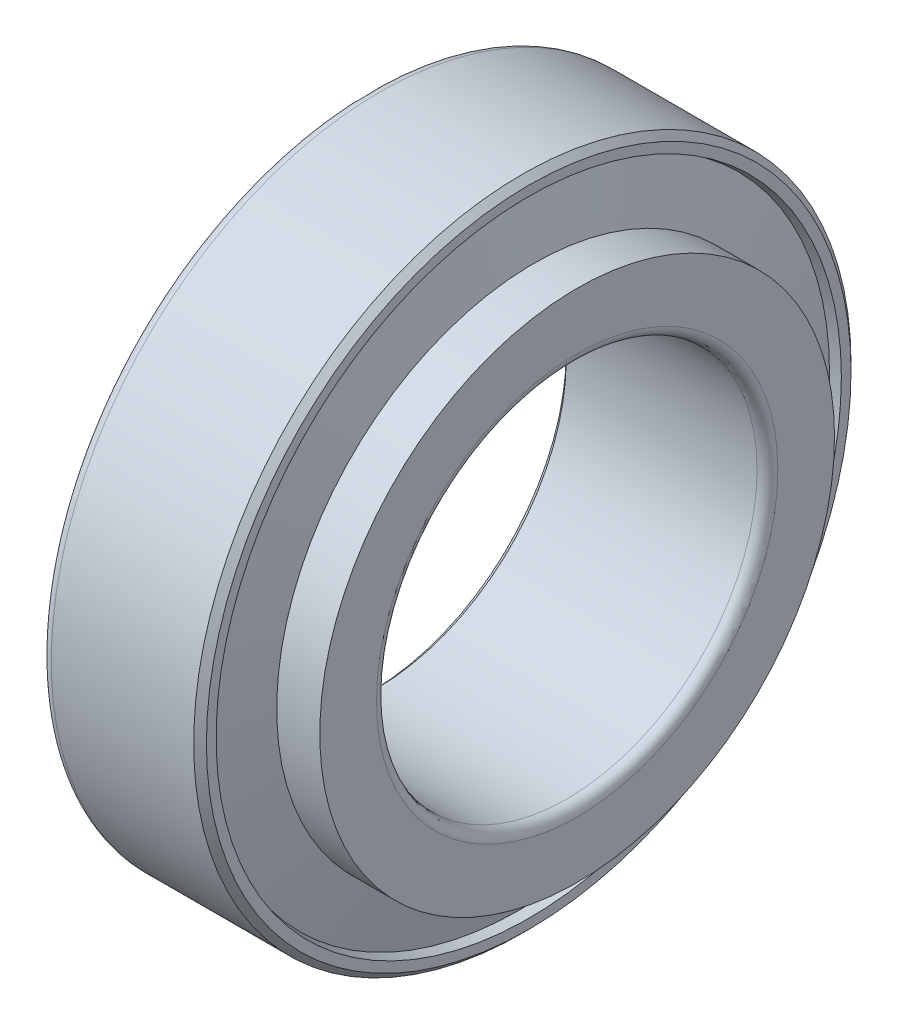
SolidWorks part; units mm, degrees
revolve "OuterRace" add sketch "OutRacSke" angle 360 about L5 other way angle 28.04 reverse direction yes
sketch "OutRacSke" plane through (0, 0, 0) normal (0, 0, 1) x (1, 0, 0)
  line L0 (-7, 45.1815) -> (-30, 39.447)
  line L1 (-30, 39.447) -> (-30, 46)
  line L2 (-28.5, 47.5) -> (-7.92, 47.5)
  line L3 (-7.92, 47.5) -> (-7, 46.58)
  line L4 (-7, 46.58) -> (-7, 45.1815)
  line L5 (-42.5, 0) -> (42.5, 0) construction
  arc A0 (-30, 46) -> (-28.5, 47.5) centre (-28.5, 46) cw
  dimension "D8" = 45
  dimension "Tangle" = 14
ref_plane "Plane1" through (0, 0, 0) normal (0, 0, 1) x (1, 0, 0)
ref_plane "Plane2" through (0, 0, 0) normal (0, 1, 0) x (1, 0, 0)
ref_plane "Plane3" through (0, 0, 0) normal (1, 0, 0) x (0, 0, -1)
sketch "Clipboard" plane through (0, 0, 0) normal (0, 0, 1) x (1, 0, 0)
  line L0 (0, 0) -> (10, 0) construction
  line L1 (0, 0) -> (78.8459, -2.7534)
  line L2 (0, 0) -> (54.9665, 1.9195)
  line L3 (0, 0) -> (94.9421, -3.3155)
  line L4 (0, 0) -> (-20.6968, -0.3613)
  line L5 (0, 0) -> (-9, 30)
  dimension "Roller_diameter" = 9
  dimension "cyl_len" = 20.7
sketch "RolDetSke" plane through (0, 0, 0) normal (0, 0, 1) x (1, 0, 0)
  line L0 (-27.4114, 35.6538) -> (-28.5, 40.0201)
  line L1 (-27.4114, 35.6538) -> (-7.3262, 40.6615)
  line L2 (-8.4149, 45.0279) -> (-7.3262, 40.6615)
  line L4 (-44.0239, 31.5118) -> (5.8616, 43.9497) construction
  line L5 (-8.4149, 45.0279) -> (-28.5, 40.0201)
  line L9 (-7, 45.1815) -> (-30, 39.447) construction
  dimension "Roller_diameter" = 9
  dimension "dy" = 40.0201
  dimension "D2" = 28.5
  dimension "cyl_len" = 20.7
revolve "RollerDetailed" [suppressed] add sketch "RolDetSke" angle 360 about L4 reverse direction yes
sketch "RolSimSke" plane through (0, 0, 0) normal (0, 0, 1) x (1, 0, 0)
  line L0 (0, 0) -> (-32, 0) construction
  line L1 (-28.5, 40.0201) -> (-8.4149, 45.0279)
  line L2 (-28.5, 40.0201) -> (-26.3227, 31.2874)
  line L3 (-26.3227, 31.2874) -> (-6.2376, 36.2952)
  line L4 (-8.4149, 45.0279) -> (-6.2376, 36.2952)
  dimension "Roller_diameter" = 9
  dimension "dy" = 40.0201
  dimension "dx" = 28.5
  dimension "Tangle" = 14
revolve "RollersSimplified" add sketch "RolSimSke" angle 360 about L0
ref_axis "Axis1" through (-50, 0, 0) along (1, 0, 0)
pattern_circular "RollersDetailed" [suppressed] count 2 every 180 about axis through (-50, 0, 0) along (1, 0, 0)
sketch "InsRacSke" plane through (0, 0, 0) normal (0, 0, 1) x (1, 0, 0)
  line L0 (-26.424, 31.7374) -> (-30, 31.7374)
  line L1 (-30, 46) -> (-30, -46) construction
  line L2 (-30, 31.7374) -> (-30, 28.42)
  line L3 (-30, 28.42) -> (-29.08, 27.5)
  line L4 (-29.08, 27.5) -> (-1.5, 27.5)
  line L5 (0, 29) -> (0, 37.1952)
  line L6 (0, 37.1952) -> (-6.2267, 37.1952)
  line L7 (-6.2267, 37.1952) -> (-6.2267, 36.2952)
  line L8 (-6.2267, 36.2952) -> (-26.3118, 31.2874)
  line L9 (-26.3118, 31.2874) -> (-26.424, 31.7374)
  line L10 (-42.5, 0) -> (42.5, 0) construction
  arc A0 (-1.5, 27.5) -> (0, 29) centre (-1.5, 29) ccw
  dimension "Tangle" = 14
  dimension "cyl_len" = 20.7
  dimension "dy" = 31.2874
  dimension "dx" = 26.3118
  dimension "D11" = 45
  dimension "D2" = 30
revolve "InnerRace" add sketch "InsRacSke" angle 360 about L10 reverse direction yes
sketch "CagSpiSke" plane through (0, 0, 0) normal (0, 0, 1) x (1, 0, 0)
  line L3 (-6.322, 40.7128) -> (-27.4114, 35.4547)
  line L4 (-27.8484, 34.7273) -> (-27.5581, 33.563)
  line L6 (-42.5, 0) -> (42.5, 0) construction
  arc A1 (-27.4114, 35.4547) -> (-27.8484, 34.7273) centre (-27.2662, 34.8725) ccw
  dimension "Tangle" = 14
  dimension "radius" = 0.6
  dimension "dx" = 27.4114
  dimension "dy" = 35.4547
  dimension "offset" = 1.8
revolve "CageSpine" [suppressed] add sketch "CagSpiSke" angle 0.001 about L6 wall 1.5
equation "\"OD@OutRacSke\" = \"Race_OD@Clipboard\""
equation "\"cup_SID@OutRacSke\" = \"Race_ID@Clipboard\""
equation "\"chamfer@OutRacSke\" = \"cup_width@OutRacSke\" / 25"
equation "\"offset@OutRacSke\" = \"OA_width@Clipboard\""
equation "\"D2@RolDetSke\" = \"offset@OutRacSke\" - \"cup_radius@OutRacSke\""
equation "\"dy@RolDetSke\" =  ( ( \"Race_ID@Clipboard\" / 2 ) + ( \"cup_radius@OutRacSke\" ) * tan(\"Tangle@OutRacSke\" * 3.141592654/180) ) * 1.005"
equation "\"cyl_len@RolDetSke\" = \"cyl_len@Clipboard\""
equation "\"Roller_diameter@RolDetSke\" = \"Roller_diameter@Clipboard\""
equation "\"dx@RolSimSke\" = \"offset@OutRacSke\" - \"cup_radius@OutRacSke\""
equation "\"dy@RolSimSke\" =  ( ( \"Race_ID@Clipboard\" / 2 ) + ( \"cup_radius@OutRacSke\" ) * tan(\"Tangle@OutRacSke\" * 3.141592654/180) ) * 1.005"
equation "\"Cyl_Len@RolSimSke\" = \"cyl_len@Clipboard\""
equation "\"Roller_diameter@RolSimSke\" = \"Roller_diameter@Clipboard\""
equation "\"Bore@InsRacSke\" = \"Bore@Clipboard\""
equation "\"Tangle@InsRacSke\" = \"Tangle@OutRacSke\""
equation "\"cyl_len@InsRacSke\" = \"cyl_len@Clipboard\""
equation "\"chamfer@InsRacSke\" = \"chamfer@OutRacSke\""
equation "\"D2@InsRacSke\" = \"OA_width@Clipboard\""
equation "\"dx@InsRacSke\" = \"offset@OutRacSke\" - \"cup_radius@OutRacSke\" -  (  \"Roller_diameter@Clipboard\" * 1.005 )  * sin(\"Tangle@InsRacSke\" * 3.141592654/180)"
equation "\"dy@InsRacSke\" = ( ( \"Race_ID@Clipboard\" / 2 ) + ( \"cup_radius@OutRacSke\" ) * tan(\"Tangle@OutRacSke\" * 3.141592654/180) ) * 1.005 -  ( \"Roller_diameter@Clipboard\" )  * cos(\"Tangle@InsRacSke\" * 3.141592654/180) "
equation "\"front_groove@InsRacSke\" = \"Groove_dp@InsRacSke\" / 2"
equation "\"Tangle@CagSpiSke\" = \"Tangle@OutRacSke\""
equation "\"dx@CagSpiSke\" = ( \"offset@OutRacSke\" - \"cup_radius@OutRacSke\" ) -  (  \"Roller_diameter@Clipboard\" / 2  )  * sin(\"Tangle@InsRacSke\" * 3.141592654/180)"
equation "\"dy@CagSpiSke\" = ( ( \"Race_ID@Clipboard\" / 2 ) + ( \"cup_radius@OutRacSke\" ) * tan(\"Tangle@OutRacSke\" * 3.141592654/180) )  -  ( \"Roller_diameter@Clipboard\" / 2 )  * cos(\"Tangle@InsRacSke\" * 3.141592654/180) "
equation "\"length@CagSpiSke\" = \"cyl_len@Clipboard\" * 1.05"
equation "\"offset@CagSpiSke\" = \"Roller_diameter@Clipboard\" / 5"
equation "\"radius@CagSpiSke\" = \"offset@CagSpiSke\" / 3"
equation "\"D3@CageSpine\" = \"Roller_diameter@Clipboard\" / 6"
equation "\"Max_count@Clipboard\" = int( 3.14159265 / atn(( \"Roller_diameter@Clipboard\" / 2) / sqr( \"dy@CagSpiSke\"  *  \"dy@CagSpiSke\" - ( \"Roller_diameter@Clipboard\" / 2) *  ( \"Roller_diameter@Clipboard\" / 2))))"
equation "\"Max_count@Clipboard\" = ((sgn( \"Max_count@Clipboard\" - \"Count@Clipboard\" )-1)*( \"Max_count@Clipboard\" - \"Count@Clipboard\" ))/-2+ \"Count@Clipboard\""
equation "\"Count@RollersDetailed\" = int( \"Show_count@Clipboard\" ) "
equation "\"Count@RollersDetailed\" = ((sgn( \"Count@RollersDetailed\" - \"Max_count@Clipboard\" )-1)*( \"Count@RollersDetailed\" - \"Max_count@Clipboard\" ))/-2+ \"Max_count@Clipboard\""
equation "\"Count@RollersDetailed\" = ((sgn( \"Count@RollersDetailed\" - \"Min_count@Clipboard\" )+1)*( \"Count@RollersDetailed\" - \"Min_count@Clipboard\"))/2 +\"Min_count@Clipboard\""
equation "\"Angle@RollersDetailed\" = 360.0 / \"Max_count@Clipboard\""
equation "\"Angle@CageSpine\" =  \"Angle@RollersDetailed\" * ( \"Count@RollersDetailed\" -1 + int( \"Count@RollersDetailed\" / \"Max_count@Clipboard\" ) )  + 0.001 -  int( \"Count@RollersDetailed\" / \"Max_count@Clipboard\" ) * 0.001"
equation "\"Angle@CageSpine\" =  \"Angle@CageSpine\" * int( \"Min_count@Clipboard\" / 2) + int(1 / \"Min_count@Clipboard\")  * 0.001"
equation "\"Tangle@RolSimSke\" = \"Tangle@OutRacSke\""
